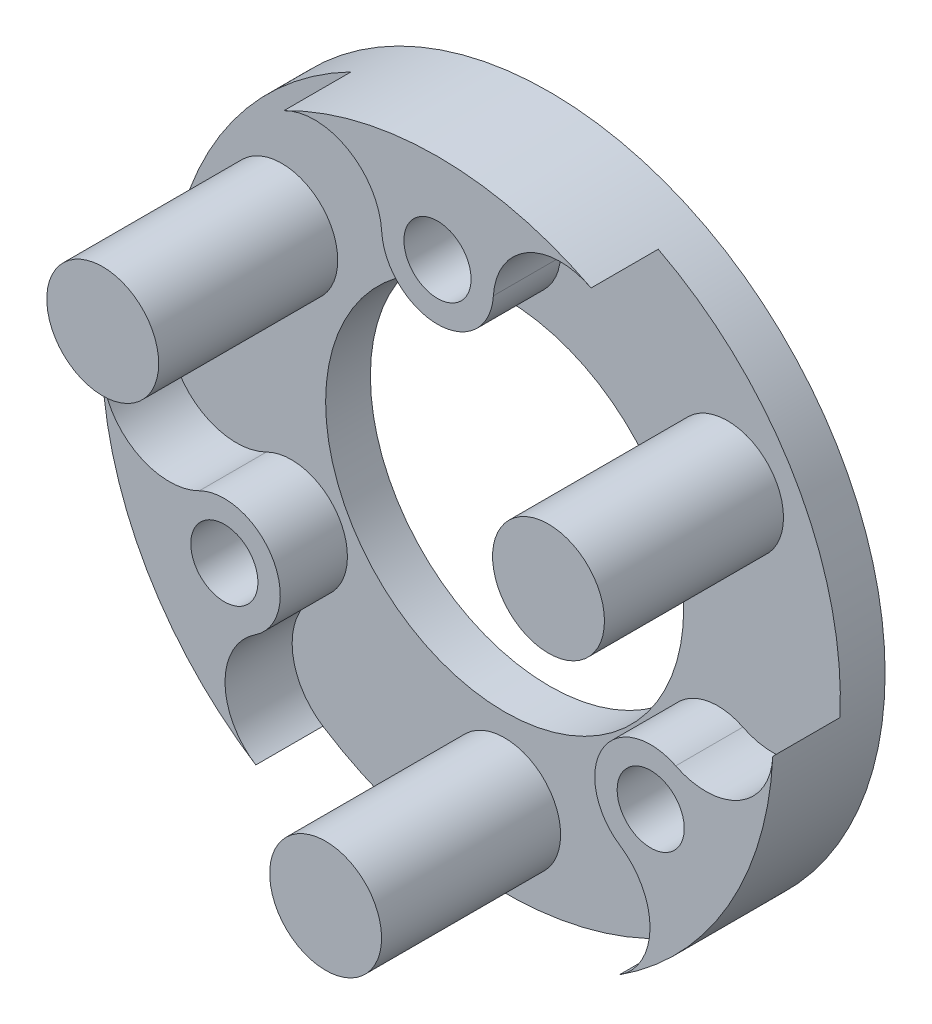
SolidWorks part; units mm, degrees
ref_plane "Front Plane" through (0, 0, 0) normal (0, 0, 1) x (1, 0, 0)
ref_plane "Top Plane" through (0, 0, 0) normal (0, 1, 0) x (1, 0, 0)
ref_plane "Right Plane" through (0, 0, 0) normal (1, 0, 0) x (0, 0, -1)
sketch "Sketch1" plane through (0, 0, 0) normal (0, 0, 1) x (1, 0, 0)
  line L0 (0, 0) -> (12.9904, 7.5) construction
  line L1 (0, 0) -> (0, 15) construction
  circle A0 centre (0, 0) radius 8
  circle A1 centre (0, 0) radius 15
  circle A2 centre (9.9593, 5.75) radius 1.5
  circle A3 centre (0, -11.5) radius 1.5
  circle A4 centre (-9.9593, 5.75) radius 1.5
  point P14 (0, 0)
  dimension "D1" = 16
  dimension "D2" = 30
  dimension "D4" = 3
  dimension "D3" = 60
  dimension "D5" = 11.5
  dimension "D6" = 3
extrude "Boss-Extrude1" add sketch "Sketch1" along normal blind 2
sketch "Sketch2" plane through (0, 0, 2) normal (0, 0, 1) x (1, 0, 0)
  circle A0 centre (0, 0) radius 8 construction
  circle A1 centre (0, 0) radius 15 construction
  circle A2 centre (0, -11.5) radius 1.5 construction
  circle A3 centre (-9.9593, 5.75) radius 1.5 construction
  circle A4 centre (9.9593, 5.75) radius 1.5 construction
  circle A5 centre (0, 0) radius 8
  circle A6 centre (0, 0) radius 15
  circle A7 centre (0, -11.5) radius 1.5
  circle A8 centre (-9.9593, 5.75) radius 1.5
  circle A9 centre (9.9593, 5.75) radius 1.5
  circle A10 centre (9.9593, 5.75) radius 2.5
  circle A11 centre (-9.9593, 5.75) radius 2.5
  circle A12 centre (0, -11.5) radius 2.5
  circle M7 centre (0, -11.5) radius 1.5
  circle M10 centre (9.9593, 5.75) radius 1.5
  circle M11 centre (-9.9593, 5.75) radius 1.5
  dimension "D1" = 5
extrude "Boss-Extrude2" add sketch "Sketch2" along normal blind 8 contours A11 M11 | A10 M10 | M11 | M10 | A12 M7 | M7 region at (0, -11.5, 2) region at (-9.9593, 5.75, 2) region at (9.9593, 5.75, 2) region at (7.53, 5.75, 2) region at (-12.3886, 5.75, 2) region at (-2.4293, -11.5, 2)
sketch "Sketch3" plane through (0, 0, 2) normal (0, 0, 1) x (1, 0, 0)
  line L0 (0, 0) -> (0, 15) construction
  circle A0 centre (0, 0) radius 8 construction
  circle A1 centre (0, 0) radius 15 construction
  circle A2 centre (0, 0) radius 8
  circle A3 centre (0, 0) radius 15
  circle A4 centre (0, -11.5) radius 2.5 construction
  circle A5 centre (9.9593, 5.75) radius 2.5 construction
  circle A6 centre (-9.9593, 5.75) radius 2.5 construction
  circle A7 centre (0, -11.5) radius 2.5
  circle A8 centre (9.9593, 5.75) radius 2.5
  circle A9 centre (-9.9593, 5.75) radius 2.5
  arc A10 (-2.4955, 10.8502) -> (2.4955, 10.8502) centre (0, 11) ccw
  arc A11 (2.4955, 10.8502) -> (6.8626, 13.3381) centre (5.4901, 10.6705) cw
  arc A12 (-2.4955, 10.8502) -> (-6.8626, 13.3381) centre (-5.4901, 10.6705) ccw
  circle A13 centre (0, 11) radius 1.5
  arc A14 (8.1488, -7.5863) -> (8.1198, -12.6123) centre (6.4958, -10.0898) cw
  arc A15 (10.6443, -3.2639) -> (8.1488, -7.5863) centre (9.5263, -5.5) ccw
  circle A16 centre (9.5263, -5.5) radius 1.5
  arc A17 (10.6443, -3.2639) -> (14.9824, -0.7258) centre (11.9859, -0.5806) ccw
  arc A18 (-10.6443, -3.2639) -> (-14.9824, -0.7258) centre (-11.9859, -0.5806) cw
  arc A19 (-8.1488, -7.5863) -> (-10.6443, -3.2639) centre (-9.5263, -5.5) ccw
  circle A20 centre (-9.5263, -5.5) radius 1.5
  arc A21 (-8.1488, -7.5863) -> (-8.1198, -12.6123) centre (-6.4958, -10.0898) ccw
  point P17 (0, 8)
  point P42 (0, 0)
  circle M9 centre (0, 0) radius 15
  dimension "D2" = 5
  dimension "D3" = 3
  dimension "D5" = 3
  dimension "D6" = 3
  dimension "D1" = 11
extrude "Boss-Extrude3" add sketch "Sketch3" along normal offset from surface (3 mm away) 5 contours A21 A19 A18 A20 M9 | A17 A15 A14 A16 M9 | A10 L0 A13 A3 A12 | L0 A10 A11 A13 M9 region at (-1.9615, 12.6326, 2) region at (1.9615, 12.6326, 2) region at (-10.9401, -6.3163, 2) region at (10.9401, -6.3163, 2) up to face at (-7.4593, 5.75, 10)
